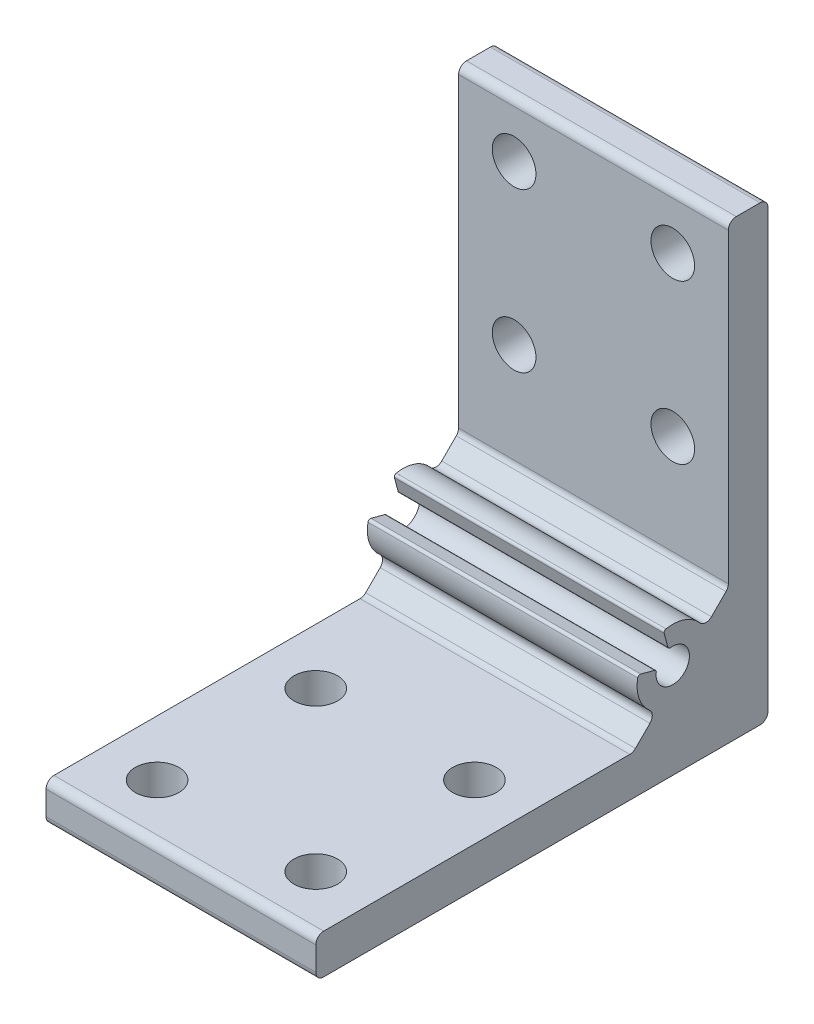
SolidWorks part; units mm, degrees
ref_plane "Front Plane" through (0, 0, 0) normal (0, 0, 1) x (1, 0, 0)
ref_plane "Top Plane" through (0, 0, 0) normal (0, 1, 0) x (1, 0, 0)
ref_plane "Right Plane" through (0, 0, 0) normal (1, 0, 0) x (0, 0, -1)
ref_plane "Plane1" through (0, 0, 0) normal (1, 0, 0) x (0, 0, -1)
sketch "Sketch1" plane through (0, 0, 0) normal (1, 0, 0) x (0, 0, -1)
  line L0 (-56, 0) -> (-1, 0)
  line L1 (0, 1) -> (0, 56)
  line L2 (-1, 57) -> (-4, 57)
  line L3 (-5, 56) -> (-5, 17.4142)
  line L4 (-5.2929, 16.7071) -> (-7.122, 14.878)
  line L5 (-13.0843, 16.0465) -> (-12.6163, 14.3)
  line L6 (-14.3, 12.6163) -> (-16.0465, 13.0843)
  line L7 (-14.878, 7.122) -> (-16.7071, 5.2929)
  line L8 (-17.4142, 5) -> (-56, 5)
  line L9 (-57, 4) -> (-57, 1)
  arc A0 (-57, 1) -> (-56, 0) centre (-56, 1) ccw
  arc A1 (-1, 0) -> (0, 1) centre (-1, 1) ccw
  arc A2 (0, 56) -> (-1, 57) centre (-1, 56) ccw
  arc A3 (-4, 57) -> (-5, 56) centre (-4, 56) ccw
  arc A4 (-5, 17.4142) -> (-5.2929, 16.7071) centre (-6, 17.4142) cw
  arc A5 (-7.122, 14.878) -> (-8.5874, 14.9333) centre (-7.8291, 15.5851) cw
  arc A6 (-8.5874, 14.9333) -> (-12.8512, 16.4188) centre (-12, 12) ccw
  arc A7 (-12.8512, 16.4188) -> (-13.0843, 16.0465) centre (-12.7945, 16.1242) ccw
  arc A8 (-12.6163, 14.3) -> (-12.2857, 14.0805) centre (-12.3265, 14.3777) ccw
  arc A9 (-12.2857, 14.0805) -> (-14.0805, 12.2857) centre (-12, 12) cw
  arc A10 (-14.0805, 12.2857) -> (-14.3, 12.6163) centre (-14.3777, 12.3265) ccw
  arc A11 (-16.0465, 13.0843) -> (-16.4188, 12.8512) centre (-16.1242, 12.7945) ccw
  arc A12 (-16.4188, 12.8512) -> (-14.9333, 8.5874) centre (-12, 12) ccw
  arc A13 (-14.9333, 8.5874) -> (-14.878, 7.122) centre (-15.5851, 7.8291) cw
  arc A14 (-16.7071, 5.2929) -> (-17.4142, 5) centre (-17.4142, 6) cw
  arc A15 (-56, 5) -> (-57, 4) centre (-56, 4) ccw
extrude "Boss-Extrude1" add sketch "Sketch1" against normal blind 17 and the other way blind 17
ref_plane "Plane2" through (0, 0, 0) normal (0, 1, 0) x (1, 0, 0)
sketch "Sketch2" plane through (0, 0, 0) normal (0, 1, 0) x (1, 0, 0)
  circle A0 centre (-10, -30) radius 2.75
extrude "Cut-Extrude1" cut sketch "Sketch2" along normal blind 5
ref_plane "Plane3" through (0, 0, 0) normal (0, 1, 0) x (1, 0, 0)
sketch "Sketch3" plane through (0, 0, 0) normal (0, 1, 0) x (1, 0, 0)
  circle A0 centre (-10, -50) radius 2.75
extrude "Cut-Extrude2" cut sketch "Sketch3" along normal blind 5
ref_plane "Plane4" through (0, 0, 0) normal (0, 1, 0) x (1, 0, 0)
sketch "Sketch4" plane through (0, 0, 0) normal (0, 1, 0) x (1, 0, 0)
  circle A0 centre (10, -30) radius 2.75
extrude "Cut-Extrude3" cut sketch "Sketch4" along normal blind 5
ref_plane "Plane5" through (0, 0, 0) normal (0, 1, 0) x (1, 0, 0)
sketch "Sketch5" plane through (0, 0, 0) normal (0, 1, 0) x (1, 0, 0)
  circle A0 centre (10, -50) radius 2.75
extrude "Cut-Extrude4" cut sketch "Sketch5" along normal blind 5
ref_plane "Plane6" through (0, 0, 0) normal (0, 0, 1) x (1, 0, 0)
sketch "Sketch6" plane through (0, 0, 0) normal (0, 0, 1) x (1, 0, 0)
  circle A0 centre (-10, 30) radius 2.75
extrude "Cut-Extrude5" cut sketch "Sketch6" along normal blind 5
ref_plane "Plane7" through (0, 0, 0) normal (0, 0, 1) x (1, 0, 0)
sketch "Sketch7" plane through (0, 0, 0) normal (0, 0, 1) x (1, 0, 0)
  circle A0 centre (10, 30) radius 2.75
extrude "Cut-Extrude6" cut sketch "Sketch7" along normal blind 5
ref_plane "Plane8" through (0, 0, 0) normal (0, 0, 1) x (1, 0, 0)
sketch "Sketch8" plane through (0, 0, 0) normal (0, 0, 1) x (1, 0, 0)
  circle A0 centre (-10, 50) radius 2.75
extrude "Cut-Extrude7" cut sketch "Sketch8" along normal blind 5
ref_plane "Plane9" through (0, 0, 0) normal (0, 0, 1) x (1, 0, 0)
sketch "Sketch9" plane through (0, 0, 0) normal (0, 0, 1) x (1, 0, 0)
  circle A0 centre (10, 50) radius 2.75
extrude "Cut-Extrude8" cut sketch "Sketch9" along normal blind 5
